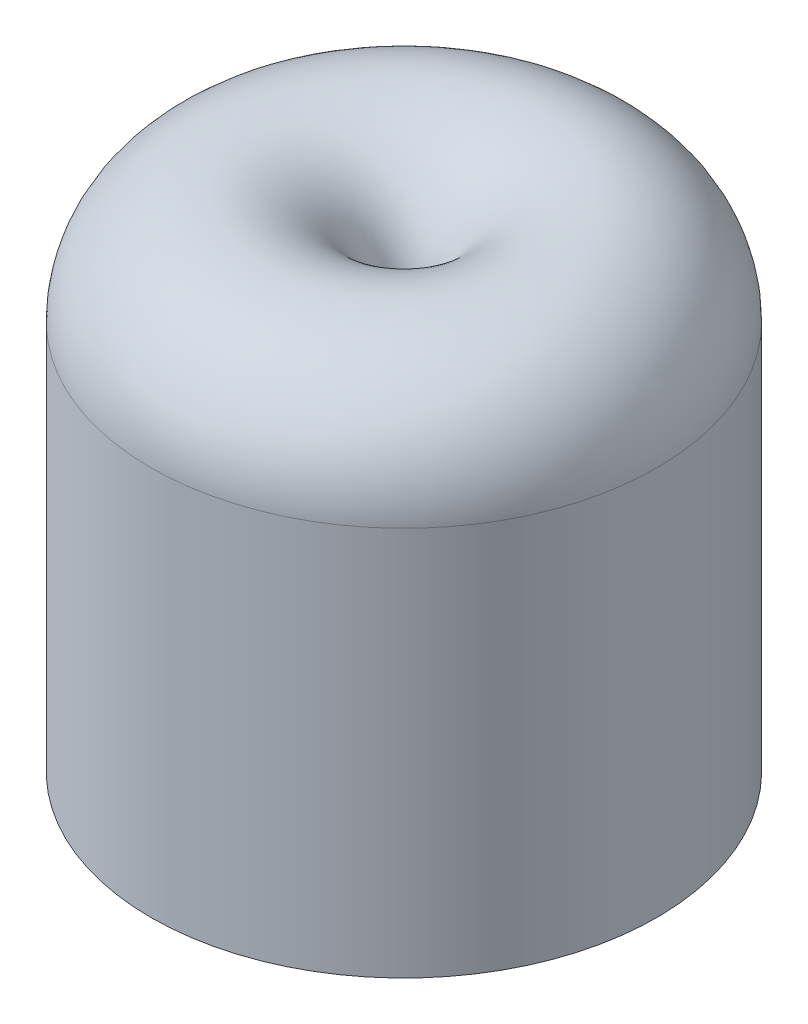
SolidWorks part; units mm, degrees
ref_plane "Front Plane" through (0, 0, 0) normal (0, 0, 1) x (1, 0, 0)
ref_plane "Top Plane" through (0, 0, 0) normal (0, 1, 0) x (1, 0, 0)
ref_plane "Right Plane" through (0, 0, 0) normal (1, 0, 0) x (0, 0, -1)
sketch "Sketch2" plane through (0, 0, 0) normal (0, 1, 0) x (1, 0, 0)
  circle A0 centre (0, 0) radius 6.35
  circle A1 centre (0, 0) radius 0.508
  dimension "D1" = 12.7
extrude "Boss-Extrude1" add sketch "Sketch2" along normal blind 12.7
fillet "Fillet7" 2 edges at (0, 12.7, 6.35) (0, 12.7, 0.508) type full round first side face at (0, 12.7, 6.35) second side face at (0, 12.7, 0.508) middle face at (0, 12.7, 6.35)
